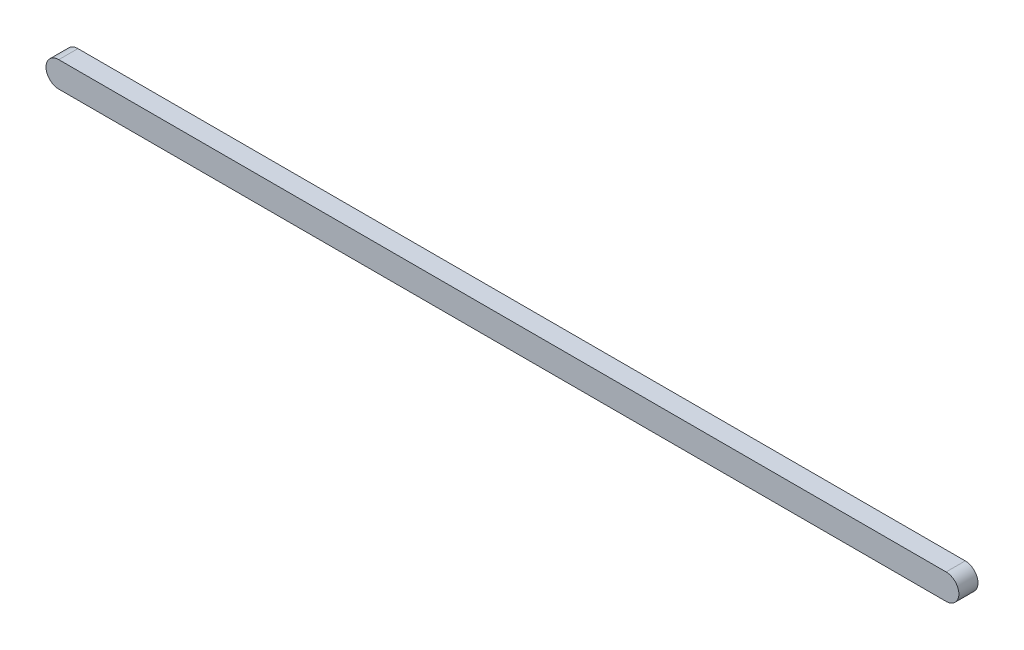
SolidWorks part; units mm, degrees
ref_plane "前视基准面" through (0, 0, 0) normal (0, 0, 1) x (1, 0, 0)
ref_plane "上视基准面" through (0, 0, 0) normal (0, 1, 0) x (1, 0, 0)
ref_plane "右视基准面" through (0, 0, 0) normal (1, 0, 0) x (0, 0, -1)
sketch "草图1" plane through (0, 0, 0) normal (0, 0, 1) x (1, 0, 0)
  line L0 (0, 0) -> (139, 0)
  line L5 (139, 4) -> (0, 4)
  arc A0 (139, 0) -> (139, 4) centre (139, 2) ccw
  arc A2 (0, 4) -> (0, 0) centre (0, 2) ccw
extrude "凸台-拉伸1" add sketch "草图1" along normal blind 3
ref_plane "基准面1" through (0, 2, 0) normal (0, -1, 0) x (-1, 0, 0)
sketch "草图2" plane through (0, 2, 0) normal (0, -1, 0) x (-1, 0, 0)
  line L0 (0, 0) -> (0, -1.5)
  line L1 (0, -1.5) -> (0, -0.5)
  line L2 (0, 0) -> (0, 1.0875) construction
  line L3 (0, 0.5) -> (0, -1.5)
  arc A0 (0, 0.5) -> (0, -1.5) centre (0, -0.5) ccw
ref_axis "基准轴2" through (0, 2, 0) along (0, 0, -1)
revolve "切除-旋转1" cut sketch "草图2" angle 360 about L2 region at (0.4244, 2, 0.5)
sketch "草图4" plane through (0, 2, 0) normal (0, -1, 0) x (-1, 0, 0)
  line L0 (0, 0) -> (-139, 0)
  line L1 (-139, 0) -> (-139, -0.5)
  line L2 (-139, -3) -> (-139, 0) construction
  line L3 (-139, -0.5) -> (-139, -1.5)
  line L4 (-139, -1.5) -> (-139, 0.5)
  arc A0 (-139, 0.5) -> (-139, -1.5) centre (-139, -0.5) ccw
revolve "切除-旋转3" cut sketch "草图4" angle 360 about L4 region at (139.4244, 2, 0.5)
